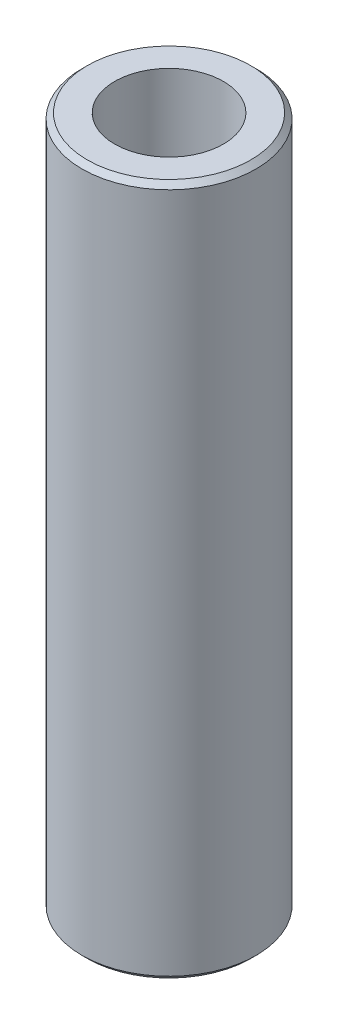
SolidWorks part; units mm, degrees
ref_plane "Front Plane" through (0, 0, 0) normal (0, 0, 1) x (1, 0, 0)
ref_plane "Top Plane" through (0, 0, 0) normal (0, 1, 0) x (1, 0, 0)
ref_plane "Right Plane" through (0, 0, 0) normal (1, 0, 0) x (0, 0, -1)
sketch "Sketch1" plane through (0, 0, 0) normal (0, 1, 0) x (1, 0, 0)
  circle A0 centre (0, 0) radius 35
  dimension "SHAFT_OD" = 70
extrude "Boss-Extrude1" add sketch "Sketch1" along normal blind 278.2305
sketch "Sketch2" plane through (0, 0, 0) normal (0, 1, 0) x (1, 0, 0)
  circle A0 centre (0, 0) radius 21.876
  dimension "BORE_D" = 43.752
extrude "Cut-Extrude1" cut sketch "Sketch2" along normal through all
chamfer "Chamfer1" distance 2.1076 angle 45 2 edges at (0, 278.2305, 35) (0, 0, 35)
